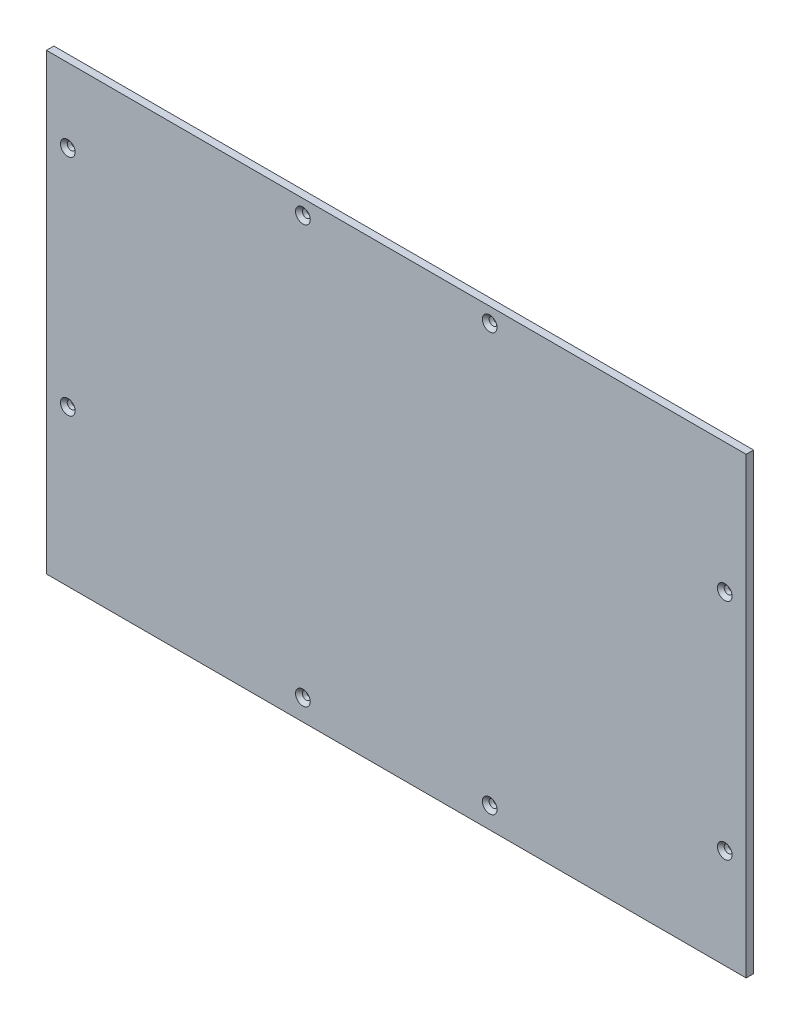
SolidWorks part; units mm, degrees
material "ABS"
ref_plane "X-Y Datum" through (0, 0, 0) normal (0, 0, 1) x (1, 0, 0)
ref_plane "X-Z Datum" through (0, 0, 0) normal (0, 1, 0) x (1, 0, 0)
ref_plane "Y-Z Datum" through (0, 0, 0) normal (1, 0, 0) x (0, 0, -1)
sketch "Sketch1" plane through (0, 0, 0) normal (0, 0, 1) x (1, 0, 0)
  line L0 (-149.85, 97.125) -> (-149.85, -97.125)
  line L1 (-149.85, 97.125) -> (149.85, 97.125)
  line L2 (-149.85, 97.125) -> (-149.85, -97.125)
  line L3 (-149.85, -97.125) -> (149.85, -97.125)
  line L4 (149.85, 97.125) -> (149.85, -97.125)
  line L5 (-149.85, 97.125) -> (149.85, -97.125) construction
  line L6 (-149.85, -97.125) -> (149.85, 97.125) construction
  line L7 (-149.85, -97.125) -> (149.85, -97.125)
  line L8 (149.85, 97.125) -> (149.85, -97.125)
  line L9 (-149.85, 97.125) -> (149.85, 97.125)
  circle A0 centre (-139.075, -86.35) radius 10.775
  circle A1 centre (-115.075, -86.35) radius 10.775 construction
  circle A2 centre (-127.075, -63.35) radius 10.775
  point P0 (0, 0)
  dimension "D1" = 21.55
  dimension "D2" = 24
  dimension "D3" = 23
  dimension "D4" = 12
  dimension "D5" = 194.25
  dimension "D6" = 299.7
  dimension "D7" = 0
extrude "Boss-Extrude1" add sketch "Sketch1" along normal blind 3.175 contours A0 L3 L4 L1 L2 A2 | A2 | A0 | A0 L2 L3 | L9 L0 L7 L8 L1 L4 L3 L2 region at (1.7533, 0.9913, 0) region at (-147.4432, -94.7182, 0) region at (-139.075, -86.35, 0) region at (-127.075, -63.35, 0)
sketch "Sketch2" plane through (0, 0, 3.175) normal (0, 0, 1) x (1, 0, 0)
  point P0 (140.6875, -54.525)
  point P1 (140.6875, 41.475)
  point P3 (-40, 90.775)
  point P5 (40, 90.775)
  point P7 (-140.6875, 65.475)
  point P9 (-140.6875, -30.525)
  point P11 (40, -88.0307)
  point P13 (-40, -88.0307)
hole_wizard "CSK for M3 Flat Head Machine Screw1" positions "Sketch3" profile "Sketch4" countersink size "M3" standard "ANSI Metric" end condition through all
sketch "Sketch3" plane through (0, 0, 3.175) normal (0, 0, 1) x (1, 0, 0)
  point P0 (-40, 90.775)
  point P3 (140.6875, 41.475)
  point P6 (140.6875, -54.525)
  point P9 (40, -88.0307)
  point P12 (-40, -88.0307)
  point P15 (-140.6875, -30.525)
  point P18 (-140.6875, 65.475)
  point P21 (40, 90.775)
sketch "Sketch4" plane through (-40, 90.775, 3.175) normal (1, 0, 0) x (0, -1, 0)
  line L0 (0, 0) -> (0, 3.175)
  line L1 (0, 3.175) -> (1.7, 3.175)
  line L2 (1.7, 3.175) -> (1.7, 1.45)
  line L3 (1.7, 1.45) -> (3.15, 0)
  line L5 (3.15, 0) -> (0, 0)
  line L6 (-1.7, 1.45) -> (-3.15, 0) construction
  line L11 (0, -6.35) -> (0, 107.95) construction
  dimension "Thru Hole Dia." = 3.4
  dimension "Thru Hole Depth" = 3.175
  dimension "Near C'Sink Dia." = 6.3
  dimension "Near C'Sink Angle" = 90
